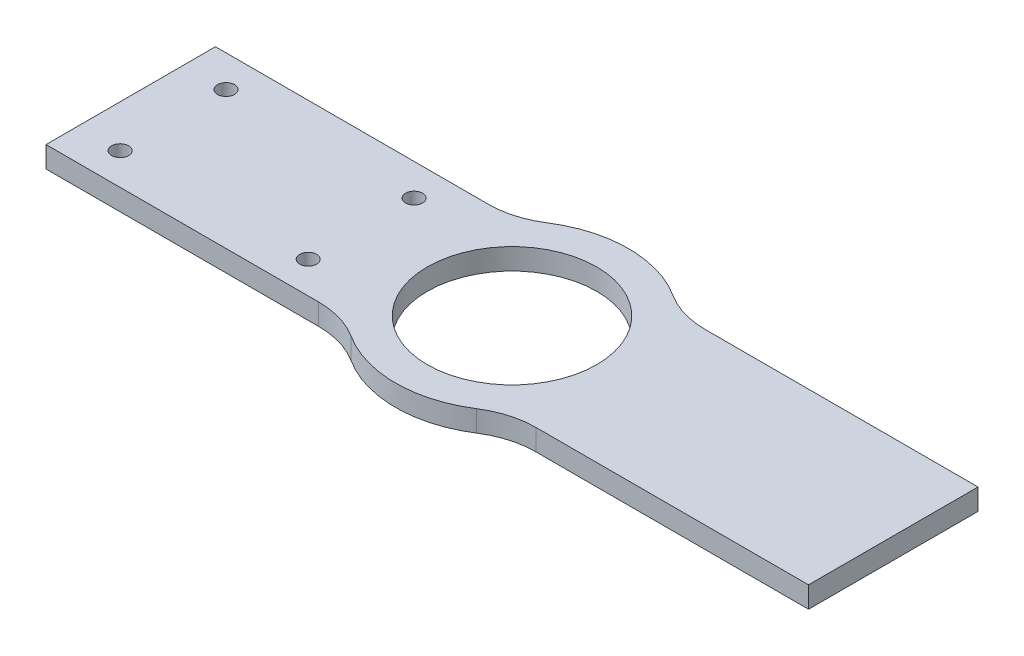
SolidWorks part; units mm, degrees
material "6061-T6 (SS)"
ref_plane "Front" through (0, 0, 0) normal (0, 0, 1) x (1, 0, 0)
ref_plane "Top" through (0, 0, 0) normal (0, 1, 0) x (1, 0, 0)
ref_plane "Right" through (0, 0, 0) normal (1, 0, 0) x (0, 0, -1)
sketch "Sketch1" plane through (0, 0, 0) normal (0, 1, 0) x (1, 0, 0)
  line L0 (228.6, 0) -> (228.6, 19.05) construction
  line L1 (0, 0) -> (81.7659, 0)
  line L2 (0, 0) -> (0, 50.8)
  line L3 (0, 50.8) -> (81.7659, 50.8)
  line L4 (228.6, 0) -> (228.6, 50.8)
  line L5 (0, 50.8) -> (228.6, 0) construction
  line L6 (146.8341, 50.8) -> (228.6, 50.8)
  line L7 (146.8341, 0) -> (228.6, 0)
  arc A0 (95.4645, -4.0105) -> (133.1355, -4.0105) centre (114.3, 25.4) ccw
  arc A1 (133.1355, 54.8105) -> (95.4645, 54.8105) centre (114.3, 25.4) ccw
  arc A2 (81.7659, 0) -> (95.4645, -4.0105) centre (81.7659, -25.4) cw
  arc A3 (146.8341, 0) -> (133.1355, -4.0105) centre (146.8341, -25.4) ccw
  arc A4 (146.8341, 50.8) -> (133.1355, 54.8105) centre (146.8341, 76.2) cw
  arc A5 (81.7659, 50.8) -> (95.4645, 54.8105) centre (81.7659, 76.2) ccw
  point P18 (138.2707, 50.8)
  dimension "D2" = 69.85
  dimension "D3" = 25.4
  dimension "D1" = 50.8
extrude "Boss-Extrude1" add sketch "Sketch1" along normal blind 6.35
sketch "Sketch4" plane through (0, 6.35, 0) normal (0, 1, 0) x (1, 0, 0)
  line L0 (0, 0) -> (12.7, 9.525) construction
  line L1 (0, 0) -> (81.7659, 0) construction
  line L6 (12.7, 9.525) -> (12.7, 41.275) construction
  line L7 (12.7, 41.275) -> (25.4, 50.8) construction
  line L8 (81.7659, 50.8) -> (0, 50.8) construction
  line L9 (40.883, 0) -> (40.883, 19.6096) construction
  point P0 (12.7, 41.275)
  point P4 (12.7, 9.525)
  point P34 (69.0659, 9.525)
  point P36 (69.0659, 41.275)
  dimension "D1" = 31.75
  dimension "D2" = 25.4
hole_wizard "#10 Clearance Hole1" positions "Sketch4" profile "Sketch3" hole size "#10" standard "ANSI Inch" end condition up to next
sketch "Sketch3" plane through (12.7, 6.35, -41.275) normal (1, 0, 0) x (0, 0, 1)
  line L0 (0, 0) -> (0, 6.35)
  line L1 (0, 6.35) -> (2.5527, 6.35)
  line L2 (2.5527, 6.35) -> (2.5527, 0)
  line L5 (2.5527, 0) -> (0, 0)
  line L11 (0, -6.35) -> (0, 107.95) construction
  dimension "Thru Hole Dia." = 5.1054
  dimension "Thru Hole Depth" = 6.35
sketch "Sketch5" plane through (0, 6.35, 0) normal (0, 1, 0) x (1, 0, 0)
  circle A0 centre (114.3, 25.4) radius 25.4
  arc A1 (133.1355, 54.8105) -> (95.4645, 54.8105) centre (114.3, 25.4) ccw construction
  dimension "D1" = 50.8
extrude "Cut-Extrude1" cut sketch "Sketch5" against normal through all
